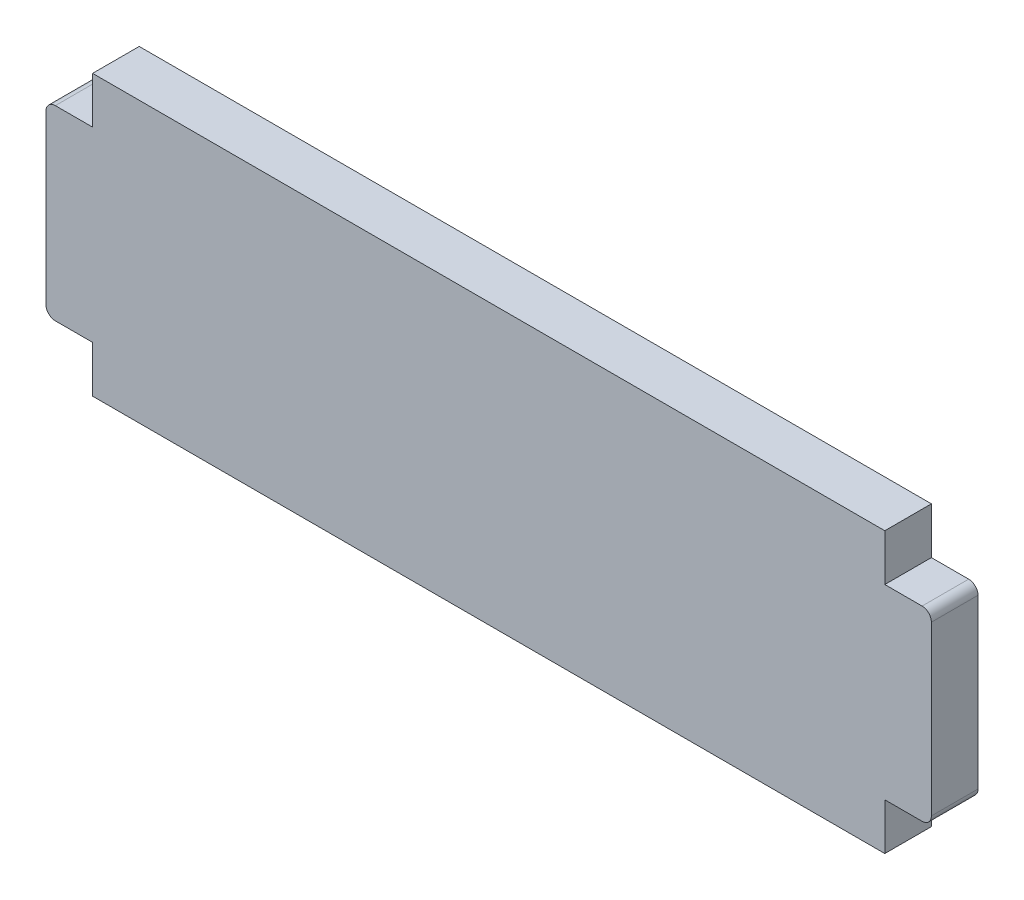
SolidWorks part; units mm, degrees
ref_plane "Front" through (0, 0, 0) normal (0, 0, 1) x (1, 0, 0)
ref_plane "Top" through (0, 0, 0) normal (0, 1, 0) x (1, 0, 0)
ref_plane "Right" through (0, 0, 0) normal (1, 0, 0) x (0, 0, -1)
sketch "Sketch1" plane through (0, 0, 0) normal (0, 0, 1) x (1, 0, 0)
  line L0 (85, 25) -> (85, 30)
  line L1 (0, 0) -> (85, 0)
  line L2 (0, 0) -> (0, 5)
  line L3 (0, 30) -> (85, 30)
  line L4 (85, 0) -> (85, 5)
  line L5 (0, 25) -> (-5, 25)
  line L7 (0, 5) -> (-5, 5)
  line L8 (-5, 25) -> (-5, 5)
  line L9 (85, 25) -> (90, 25)
  line L11 (85, 5) -> (90, 5)
  line L12 (90, 25) -> (90, 5)
  line L13 (0, 25) -> (0, 30)
  dimension "D1" = 85
  dimension "D2" = 30
  dimension "D3" = 5
  dimension "D4" = 5
  dimension "D5" = 20
  dimension "D6" = 5
  dimension "D7" = 5
  dimension "D8" = 20
extrude "Boss-Extrude1" add sketch "Sketch1" along normal blind 5
fillet "Fillet1" radius 1 4 edges at (-5, 5, 2.5) (-5, 25, 2.5) (90, 5, 2.5) (90, 25, 2.5)
